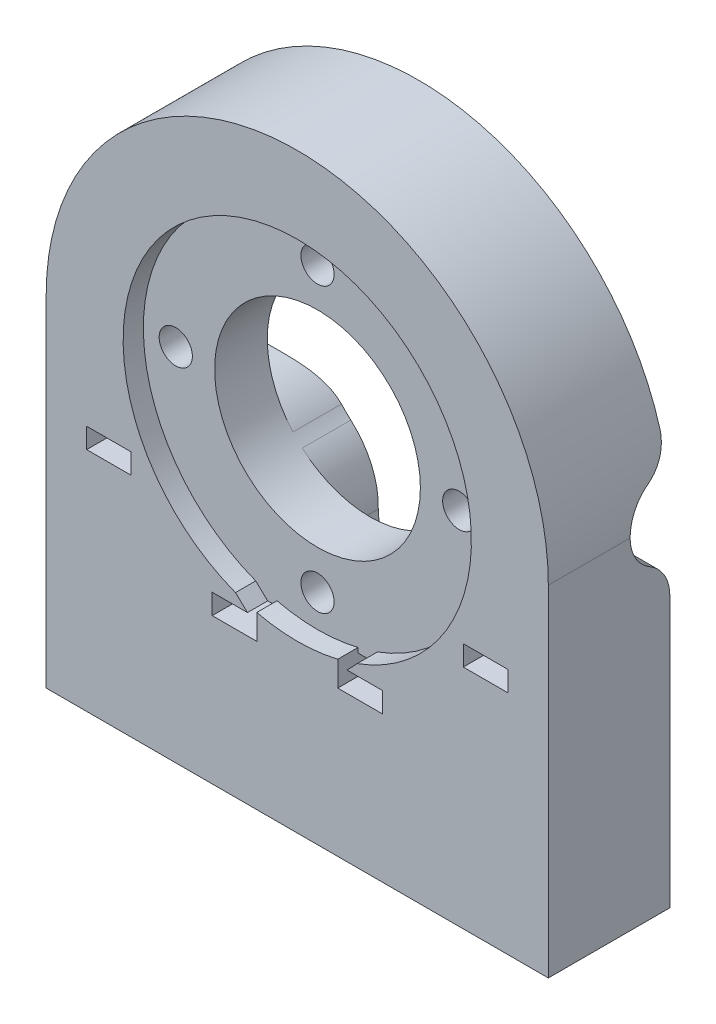
SolidWorks part; units mm, degrees
note: The reader was unsure of these and kept them because the rebuilt part matched: shared geometry of "Sketch1<3>", "Sketch1<4>", "Sketch2<3>".
ref_plane "Front Plane" through (0, 0, 0) normal (1, 0, 0) x (0, 1, 0)
ref_plane "Top Plane" through (0, 0, 0) normal (0, 0, 1) x (0, 1, 0)
ref_plane "Right Plane" through (0, 0, 0) normal (0, 1, 0) x (-1, 0, 0)
sketch "Sketch1" plane through (0, 0, 0) normal (0, 0, 1) x (0, 1, 0)
  line L0 (0, 0) -> (42, 0) construction
  line L1 (0, 31) -> (0, -31)
  line L2 (0, 31) -> (42, 31)
  line L3 (0, -31) -> (42, -31)
  circle A0 centre (42, 0) radius 12.7021
  arc A1 (42, -31) -> (42, 31) centre (42, 0) ccw
  circle A2 centre (42, 0) radius 17.5
  circle A3 centre (59.5, 0) radius 2.05
  circle A4 centre (59.5, 0) radius 5
  circle A5 centre (42, -17.5) radius 5
  circle A6 centre (42, -17.5) radius 2.05
  circle A7 centre (24.5, 0) radius 5
  circle A8 centre (24.5, 0) radius 2.05
  circle A9 centre (42, 17.5) radius 5
  circle A10 centre (42, 17.5) radius 2.05
  point P7 (0, 0)
  dimension "D3" = 35
  dimension "D4" = 4.1
  dimension "D5" = 10
  dimension "D1" = 42
  dimension "D2" = 62
  dimension "D6" = 4
extrude "Boss-Extrude1" add sketch "Sketch1" along normal blind 15
extrude "Cut-Extrude1" cut sketch "Sketch1<3>" along normal offset from surface (6 mm away) 9 contours A7 | A9 | A4 | A5 up to face at (12.7021, 42, 15)
sketch "Sketch1<3>" plane through (0, 0, 0) normal (0, 0, 1) x (0, 1, 0) same geometry as "Sketch1"
extrude "Cut-Extrude3" cut sketch "Sketch1<4>" along normal through all and the other way through all contours A6 | A3 | A10 | A8
sketch "Sketch1<4>" plane through (0, 0, 0) normal (0, 0, 1) x (0, 1, 0) same geometry as "Sketch1"
fillet "Fillet1" radius 10 8 edges at (-1.1976, 29.3545, 3) (1.1976, 29.3545, 3) (-12.6455, 40.8024, 3) (-12.6455, 43.1976, 3) (-1.1976, 54.6455, 3) (1.1976, 54.6455, 3) (12.6455, 43.1976, 3) (12.6455, 40.8024, 3)
sketch "Sketch2" plane through (0, 0, 0) normal (0, -1, 0) x (1, 0, 0)
  line L0 (-31, 7.5) -> (-23.25, 7.5) construction
  line L1 (-31, 15) -> (-31, 0) construction
  line L2 (-23.25, 7.5) -> (-23.25, 5.5468) construction
  line L3 (-22.3323, 6.1894) -> (-23.25, 5.5468)
  line L4 (-24.1677, 6.1894) -> (-23.25, 5.5468)
  line L5 (-8.6677, 6.1894) -> (-7.75, 5.5468)
  line L6 (-6.8323, 6.1894) -> (-7.75, 5.5468)
  line L7 (6.8323, 6.1894) -> (7.75, 5.5468)
  line L8 (8.6677, 6.1894) -> (7.75, 5.5468)
  line L9 (22.3323, 6.1894) -> (23.25, 5.5468)
  line L10 (24.1677, 6.1894) -> (23.25, 5.5468)
  arc A0 (-22.3323, 6.1894) -> (-24.1677, 6.1894) centre (-23.25, 7.5) ccw
  arc A1 (-6.8323, 6.1894) -> (-8.6677, 6.1894) centre (-7.75, 7.5) ccw
  arc A2 (8.6677, 6.1894) -> (6.8323, 6.1894) centre (7.75, 7.5) ccw
  arc A3 (24.1677, 6.1894) -> (22.3323, 6.1894) centre (23.25, 7.5) ccw
  dimension "D2" = 3.2
  dimension "D1" = 7.75
  dimension "D3" = 55
  dimension "D4" = 4
sketch "Sketch3" plane through (0, 0, 15) normal (0, 0, 1) x (1, 0, 0)
  line L0 (-23.25, 28) -> (-23.25, 0)
  line L1 (-26, 30.5) -> (-20.5, 30.5)
  line L2 (-26, 30.5) -> (-26, 28)
  line L3 (-26, 28) -> (-20.5, 28)
  line L4 (-20.5, 30.5) -> (-20.5, 28)
  line L5 (-26, 30.5) -> (-20.5, 28) construction
  line L6 (-26, 28) -> (-20.5, 30.5) construction
  line L7 (-10.5, 20.5) -> (-5, 20.5)
  line L8 (-10.5, 20.5) -> (-10.5, 18)
  line L9 (-10.5, 18) -> (-5, 18)
  line L10 (-5, 20.5) -> (-5, 18)
  line L11 (-10.5, 20.5) -> (-5, 18) construction
  line L12 (-10.5, 18) -> (-5, 20.5) construction
  line L13 (5, 20.5) -> (10.5, 20.5)
  line L14 (5, 20.5) -> (5, 18)
  line L15 (5, 18) -> (10.5, 18)
  line L16 (10.5, 20.5) -> (10.5, 18)
  line L17 (5, 20.5) -> (10.5, 18) construction
  line L18 (5, 18) -> (10.5, 20.5) construction
  line L19 (20.5, 30.5) -> (26, 30.5)
  line L20 (20.5, 30.5) -> (20.5, 28)
  line L21 (20.5, 28) -> (26, 28)
  line L22 (26, 30.5) -> (26, 28)
  line L23 (20.5, 30.5) -> (26, 28) construction
  line L24 (20.5, 28) -> (26, 30.5) construction
  line L25 (-7.75, 18) -> (-7.75, 0)
  line L26 (7.75, 18) -> (7.75, 0)
  line L27 (23.25, 28) -> (23.25, 0)
  point P0 (23.25, 0)
  point P2 (7.75, 0)
  point P4 (-7.75, 0)
  point P6 (-23.25, 0)
  point P8 (-23.25, 29.25)
  point P13 (-7.75, 19.25)
  point P18 (7.75, 19.25)
  point P23 (23.25, 29.25)
  dimension "D1" = 5.5
  dimension "D2" = 5.5
  dimension "D3" = 5.5
  dimension "D4" = 5.5
  dimension "D5" = 2.5
  dimension "D6" = 2.5
  dimension "D7" = 2.5
  dimension "D8" = 2.5
  dimension "D9" = 28
  dimension "D10" = 18
extrude "Cut-Extrude12" cut sketch "Sketch3" against normal blind 2.75 and the other way through all from offset 7.5 contours L3 L4 L1 L2 | L22 L21 L20 L19 | L10 L9 L8 L7 | L14 L15 L16 L13 offset against normal yes
extrude "Cut-Extrude13" cut sketch "Sketch2" against normal offset from surface (31.5 mm away) 1 contours A0 L4 L3 | A3 L9 L10 up to face at (-23.25, 30.5, 9.875) offset beyond the face yes
extrude "Cut-Extrude14" cut sketch "Sketch2<3>" against normal offset from surface (21.5 mm away) 1 contours A1 L5 L6 | A2 L7 L8 up to face at (-7.75, 20.5, 9.875) offset beyond the face yes
sketch "Sketch2<3>" plane through (0, 0, 0) normal (0, -1, 0) x (1, 0, 0) same geometry as "Sketch2"
sketch "Sketch4" plane through (-31, 0, 0) normal (-1, 0, 0) x (0, -1, 0)
  line L0 (-42, 15) -> (-42, 0) construction
  line L1 (-50.3889, 6) -> (-33.6111, 6) construction
  line L2 (-50.3889, 6) -> (-33.6111, 6)
  circle A0 centre (-42, -0.1) radius 5
  dimension "D1" = 10
  dimension "D2" = 6.1
extrude "Cut-Extrude15" cut sketch "Sketch4" against normal through all both and the other way through all contours A0
fillet "Fillet2" radius 5 4 edges at (-24.3, 37.001, 0) (-24.0971, 46.999, 0) (24.3, 37.001, 0) (24.0971, 46.999, 0)
sketch "Sketch5" plane through (0, 0, 0) normal (0, 0, -1) x (1, 0, 0)
  line L36 (-26, -30.5) -> (-20.5, -30.5)
  line L37 (-20.5, -30.5) -> (-20.5, -28)
  line L38 (-20.5, -28) -> (-26, -28)
  line L39 (-26, -28) -> (-26, -30.5)
  line L40 (-26, -30.5) -> (-20.5, -30.5)
  line L41 (-20.5, -30.5) -> (-20.5, -28)
  line L42 (-20.5, -28) -> (-26, -28)
  line L43 (-26, -28) -> (-26, -30.5)
  line L44 (20.5, -30.5) -> (26, -30.5)
  line L45 (26, -30.5) -> (26, -28)
  line L46 (26, -28) -> (20.5, -28)
  line L47 (20.5, -28) -> (20.5, -30.5)
  line L48 (20.5, -30.5) -> (26, -30.5)
  line L49 (26, -30.5) -> (26, -28)
  line L50 (26, -28) -> (20.5, -28)
  line L51 (20.5, -28) -> (20.5, -30.5)
  line L52 (5, -20.5) -> (10.5, -20.5)
  line L53 (10.5, -20.5) -> (10.5, -18)
  line L54 (10.5, -18) -> (5, -18)
  line L55 (5, -18) -> (5, -20.5)
  line L56 (5, -20.5) -> (10.5, -20.5)
  line L57 (10.5, -20.5) -> (10.5, -18)
  line L58 (10.5, -18) -> (5, -18)
  line L59 (5, -18) -> (5, -20.5)
  line L60 (-10.5, -20.5) -> (-5, -20.5)
  line L61 (-10.5, -18) -> (-10.5, -20.5)
  line L62 (-5, -18) -> (-10.5, -18)
  line L63 (-5, -20.5) -> (-5, -18)
  line L64 (-10.5, -20.5) -> (-5, -20.5)
  line L65 (-10.5, -18) -> (-10.5, -20.5)
  line L66 (-5, -18) -> (-10.5, -18)
  line L67 (-5, -20.5) -> (-5, -18)
  circle A0 centre (-23.25, -30.5) radius 1.6
  circle A1 centre (-7.75, -20.5) radius 1.6
  circle A2 centre (7.75, -20.5) radius 1.6
  circle A3 centre (23.25, -30.5) radius 1.6
  dimension "D1" = 3.2
  dimension "D2" = 0
  dimension "D3" = 0
  dimension "D4" = 0
  dimension "D5" = 0
sketch "Sketch6" plane through (0, 0, 15) normal (0, 0, 1) x (1, 0, 0)
  line L0 (-6.15, 20.5) -> (-7.6277, 21.8985)
  line L1 (6.15, 20.5) -> (7.3897, 21.8098)
  line L2 (-6.15, 20.5) -> (-5, 20.5)
  line L3 (-5, 20.5) -> (-5, 21.0895)
  line L4 (6.15, 20.5) -> (5, 20.5)
  line L5 (5, 20.5) -> (5, 21.0895)
  circle A0 centre (0, 42) radius 21.5
  dimension "D1" = 43
extrude "Cut-Extrude17" cut sketch "Sketch6" against normal blind 2.5
